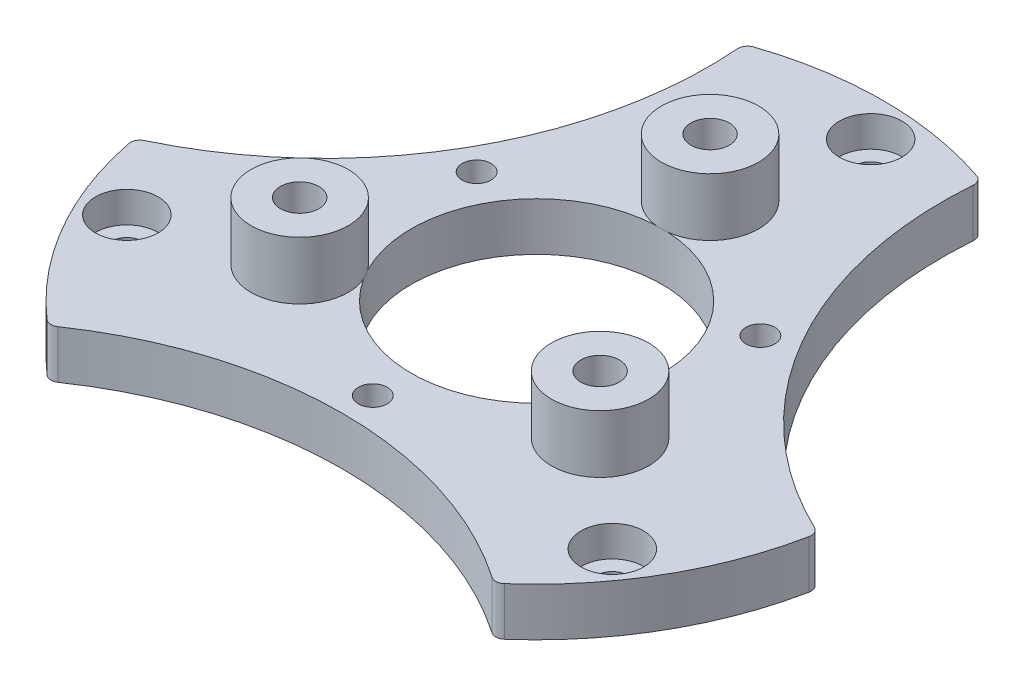
SolidWorks part; units mm, degrees
ref_plane "Front Plane" through (0, 0, 0) normal (0, 0, 1) x (1, 0, 0)
ref_plane "Top Plane" through (0, 0, 0) normal (0, 1, 0) x (1, 0, 0)
ref_plane "Right Plane" through (0, 0, 0) normal (1, 0, 0) x (0, 0, -1)
sketch "Sketch1" plane through (0, 0, 0) normal (0, 1, 0) x (1, 0, 0)
  circle A0 centre (0, 0) radius 36
  circle A1 centre (0, 0) radius 13
  dimension "D1" = 72
  dimension "D2" = 26
extrude "Boss-Extrude1" add sketch "Sketch1" along normal blind 5
sketch "Sketch2" plane through (0, 5, 0) normal (0, 1, 0) x (1, 0, 0)
  line L0 (0, -1000) -> (0, 49000) construction
  line L1 (2.789, 31.8782) -> (0, 0) construction
  circle A0 centre (2.789, 31.8782) radius 1.65
  dimension "D1" = 3.3
  dimension "D2" = 32
  dimension "D3" = 5
extrude "Cut-Extrude1" cut sketch "Sketch2" against normal through all
pattern_circular "CirPattern1" count 3 over 360 about axis through (0, 5, 0) along (0, -1, 0) of "Cut-Extrude1" reverse direction yes
sketch "Sketch10" plane through (0, 5, 0) normal (0, 1, 0) x (1, 0, 0)
  line L0 (0, 0) -> (17101.0072, 46984.631) construction
  line L1 (0, 0) -> (-17101.0072, 46984.631) construction
  line L2 (0, 0) -> (0, 50000) construction
  line L3 (-9.5766, 26.3114) -> (-12.3127, 33.8289)
  line L4 (9.5766, 26.3114) -> (12.3127, 33.8289)
  line L5 (17.9981, -21.4492) -> (23.1404, -27.5776)
  line L6 (27.5746, -4.8621) -> (35.4531, -6.2513)
  line L7 (-27.5746, -4.8621) -> (-35.4531, -6.2513)
  line L8 (-17.9981, -21.4492) -> (-23.1404, -27.5776)
  arc A0 (-12.3127, 33.8289) -> (12.3127, 33.8289) centre (0, 0) cw
  circle A1 centre (0, 0) radius 36 construction
  arc A2 (-9.5766, 26.3114) -> (9.5766, 26.3114) centre (0, 0) cw
  arc A3 (35.4531, -6.2513) -> (23.1404, -27.5776) centre (0, 0) cw
  arc A4 (27.5746, -4.8621) -> (17.9981, -21.4492) centre (0, 0) cw
  arc A5 (-23.1404, -27.5776) -> (-35.4531, -6.2513) centre (0, 0) cw
  arc A6 (-17.9981, -21.4492) -> (-27.5746, -4.8621) centre (0, 0) cw
  point P26 (0, 0)
  dimension "D1" = 20
  dimension "D2" = 20
  dimension "D3" = 8
  dimension "D4" = 3
sketch "Sketch3" plane through (0, 5, 0) normal (0, 1, 0) x (1, 0, 0)
  line L0 (0, 0) -> (51.9615, 30) construction
  line L1 (-1000, 0) -> (49000, 0) construction
  circle A0 centre (51.9615, 30) radius 39.8333
  dimension "D3" = 60
extrude "Cut-Extrude2" cut sketch "Sketch3" against normal blind 10
pattern_circular "CirPattern2" count 3 over 360 about axis through (0, 5, 0) along (0, -1, 0) of "Cut-Extrude2"
fillet "Fillet1" radius 1 6 edges at (23.1404, 2.5, 27.5776) (-23.1404, 2.5, 27.5776) (-35.4531, 2.5, 6.2513) (-12.3127, 2.5, -33.8289) (35.4531, 2.5, 6.2513) (12.3127, 2.5, -33.8289)
sketch "Sketch4" plane through (0, 5, 0) normal (0, 1, 0) x (1, 0, 0)
  circle A0 centre (0, 0) radius 6 construction
  circle A1 centre (0, 18) radius 12 construction
  circle A2 centre (0, 18) radius 5.05
  dimension "D1" = 12
  dimension "D2" = 24
  dimension "D3" = 10.1
extrude "Boss-Extrude2" add sketch "Sketch4" along normal blind 6
sketch "Sketch7" plane through (0, 5, 0) normal (0, 1, 0) x (1, 0, 0)
  circle A0 centre (2.789, 31.8782) radius 3.25
  dimension "D1" = 6.5
extrude "Cut-Extrude5" cut sketch "Sketch7" against normal blind 3.2
pattern_circular "CirPattern3" count 3 over 360 about axis through (0, 5, 0) along (0, -1, 0) of "Cut-Extrude5", "Boss-Extrude2" reverse direction yes
sketch "Sketch8" plane through (0, 5, 0) normal (0, 1, 0) x (1, 0, 0)
  line L0 (14.7224, 8.5) -> (0, 0) construction
  line L1 (-1000, 0) -> (49000, 0) construction
  circle A0 centre (14.7224, 8.5) radius 1.5
  dimension "D3" = 3
  dimension "D1" = 30
  dimension "D2" = 17
extrude "Cut-Extrude6" cut sketch "Sketch8" against normal blind 10
sketch "Sketch12" plane through (0, 11, 0) normal (0, 1, 0) x (1, 0, 0)
  circle A0 centre (0, 18) radius 2
  dimension "D1" = 4
extrude "Cut-Extrude8" cut sketch "Sketch12" against normal through all
pattern_circular "CirPattern4" count 3 over 360 about axis through (0, 5, 0) along (0, -1, 0) of "Cut-Extrude6", "Cut-Extrude8" reverse direction yes
sketch "Sketch9" plane through (0, 5, 0) normal (0, 1, 0) x (1, 0, 0)
  line L0 (-5.7304, 32.4987) -> (0, 0) construction
  line L1 (-25.7839, 33.0244) -> (49214.6038, 8715.4333) construction
  line L2 (-23.1208, 32.4785) -> (49217.2669, 8714.8874) construction
  line L3 (0, -1000) -> (0, 49000) construction
  circle A0 centre (-5.7304, 32.4987) radius 4 construction
  circle A1 centre (-5.7304, 32.4987) radius 1.65
  arc A2 (11.5708, 34.0898) -> (-11.5708, 34.0898) centre (0, 0) ccw construction
  dimension "D1" = 8
  dimension "D2" = 3.3
  dimension "D3" = 1
  dimension "D4" = 10
